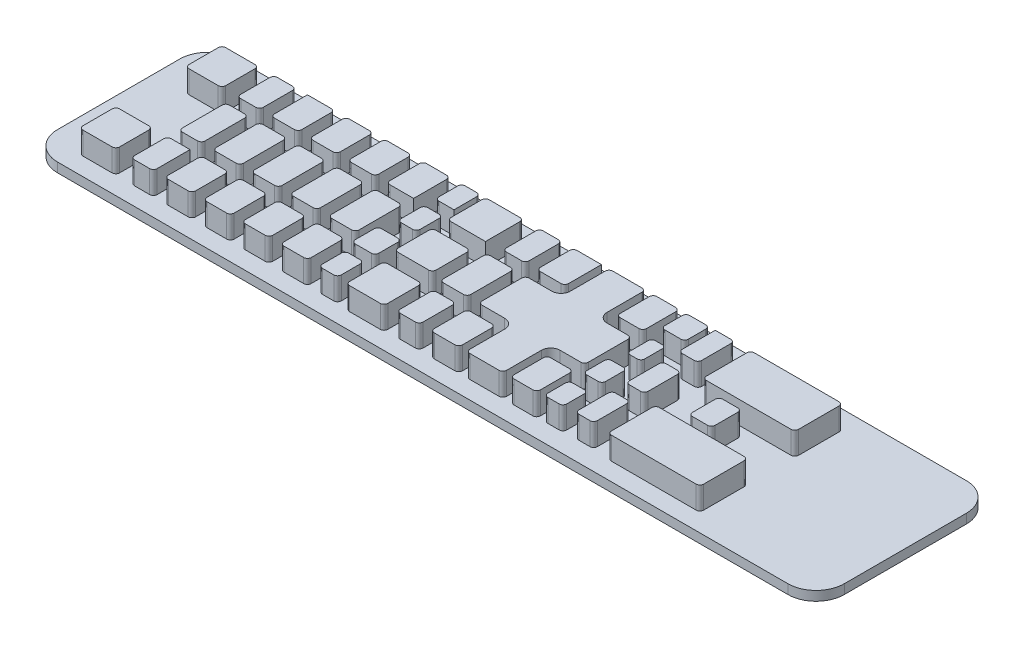
SolidWorks part; units mm, degrees
material "PVB"
ref_plane "Front Plane" through (0, 0, 0) normal (0, 0, 1) x (1, 0, 0)
ref_plane "Top Plane" through (0, 0, 0) normal (0, 1, 0) x (1, 0, 0)
ref_plane "Right Plane" through (0, 0, 0) normal (1, 0, 0) x (0, 0, -1)
ref_axis "X-axis" through (-88.99, 0, 0) along (1, 0, 0)
ref_axis "Y-axis" through (0, 55, 0) along (0, -1, 0)
ref_axis "Z-axis" through (0, 0, -88.99) along (0, 0, 1)
sketch "Sketch1" plane through (0, 0, 0) normal (0, 1, 0) x (1, 0, 0)
  line L1 (107.95, 25.4) -> (-107.95, 25.4)
  line L2 (107.95, 25.4) -> (107.95, -25.4)
  line L3 (107.95, -25.4) -> (-107.95, -25.4)
  line L4 (-107.95, 25.4) -> (-107.95, -25.4)
  line L5 (107.95, 25.4) -> (-107.95, -25.4) construction
  line L6 (107.95, -25.4) -> (-107.95, 25.4) construction
  point P0 (0, 0)
  dimension "D1" = 215.9
  dimension "D2" = 50.8
extrude "Boss-Extrude1" add sketch "Sketch1" along normal blind 2.54
sketch "Sketch4" plane through (0, 2.54, 0) normal (0, 1, 0) x (1, 0, 0)
  line L0 (-98.044, 19.304) -> (-98.044, 9.398)
  line L1 (107.95, 25.4) -> (-107.95, 25.4) construction
  line L2 (-107.95, -25.4) -> (107.95, -25.4) construction
  line L3 (-107.95, 25.4) -> (-107.95, -25.4) construction
  line L4 (-88.138, 19.304) -> (-88.138, 9.398)
  line L5 (-84.074, 19.304) -> (-84.074, 9.398)
  line L6 (-77.978, 19.304) -> (-77.978, 9.398)
  line L7 (-74.93, 19.304) -> (-74.93, 9.398)
  line L8 (-67.564, 19.304) -> (-67.564, 9.398)
  line L9 (-64.516, 19.304) -> (-64.516, 9.398)
  line L10 (-57.15, 19.304) -> (-57.15, 9.398)
  line L11 (-54.102, 19.304) -> (-54.102, 9.398)
  line L12 (-46.736, 19.304) -> (-46.736, 9.398)
  line L13 (-43.688, 19.304) -> (-43.688, 9.398)
  line L14 (-36.322, 19.304) -> (-36.322, 9.398)
  line L15 (-33.274, 19.304) -> (-33.274, 12.192)
  line L16 (36.83, 19.304) -> (36.83, 9.398)
  line L17 (33.782, 19.304) -> (33.782, 12.192)
  line L18 (28.702, 19.304) -> (28.702, 12.192)
  line L19 (25.654, 19.304) -> (25.654, 9.398)
  line L20 (18.542, 19.304) -> (18.542, 9.398)
  line L21 (16.51, 19.304) -> (16.51, 6.35)
  line L22 (6.604, 19.304) -> (6.604, 6.35)
  line L23 (-28.194, 19.304) -> (-28.194, 12.192)
  line L24 (-25.146, 19.304) -> (-25.146, 9.398)
  line L25 (-15.24, 19.304) -> (-15.24, 8.8607)
  line L26 (-12.192, 19.304) -> (-12.192, -6.35)
  line L27 (-6.096, 19.304) -> (-6.096, -6.35)
  line L28 (-3.048, 19.304) -> (-3.048, 9.398)
  line L29 (4.572, 19.304) -> (4.572, 9.398)
  line L30 (-98.044, 19.304) -> (-88.138, 19.304)
  line L31 (-98.044, -19.304) -> (-88.138, -19.304)
  line L32 (-98.044, -9.398) -> (-88.138, -9.398)
  line L33 (-98.044, 9.398) -> (-88.138, 9.398)
  line L34 (-33.274, 9.144) -> (-28.194, 9.144)
  line L35 (-33.274, -9.144) -> (-28.194, -9.144)
  line L36 (-84.074, -19.304) -> (-77.978, -19.304)
  line L37 (-84.074, -9.398) -> (-77.978, -9.398)
  line L38 (-84.074, -6.35) -> (-77.978, -6.35)
  line L39 (-84.074, 9.398) -> (-77.978, 9.398)
  line L40 (-84.074, 6.35) -> (-77.978, 6.35)
  line L41 (-84.074, 19.304) -> (-77.978, 19.304)
  line L42 (-43.688, -19.304) -> (-36.322, -19.304)
  line L43 (-43.688, -9.398) -> (-36.322, -9.398)
  line L44 (-43.688, -6.35) -> (-36.322, -6.35)
  line L45 (-43.688, 6.35) -> (-36.322, 6.35)
  line L46 (-43.688, 9.398) -> (-36.322, 9.398)
  line L47 (-54.102, -19.304) -> (-46.736, -19.304)
  line L48 (-54.102, -9.398) -> (-46.736, -9.398)
  line L49 (-54.102, -6.35) -> (-46.736, -6.35)
  line L50 (-54.102, 6.35) -> (-46.736, 6.35)
  line L51 (-54.102, 9.398) -> (-46.736, 9.398)
  line L52 (-64.516, -19.304) -> (-57.15, -19.304)
  line L53 (-64.516, -9.398) -> (-57.15, -9.398)
  line L54 (-64.516, -6.35) -> (-57.15, -6.35)
  line L55 (-64.516, 6.35) -> (-57.15, 6.35)
  line L56 (-64.516, 9.398) -> (-57.15, 9.398)
  line L57 (-74.93, -19.304) -> (-67.564, -19.304)
  line L58 (-74.93, -9.398) -> (-67.564, -9.398)
  line L59 (-74.93, -6.35) -> (-67.564, -6.35)
  line L60 (-74.93, 6.35) -> (-67.564, 6.35)
  line L61 (-74.93, 9.398) -> (-67.564, 9.398)
  line L62 (-74.93, 19.304) -> (-67.564, 19.304)
  line L63 (-64.516, 19.304) -> (-57.15, 19.304)
  line L64 (-54.102, 19.304) -> (-46.736, 19.304)
  line L65 (-43.688, 19.304) -> (-36.322, 19.304)
  line L66 (-98.044, -9.398) -> (-98.044, -19.304)
  line L67 (-88.138, -9.398) -> (-88.138, -19.304)
  line L68 (-33.274, 12.192) -> (-28.194, 12.192)
  line L69 (-33.274, -2.032) -> (-28.194, -2.032)
  line L70 (-33.274, 2.032) -> (-28.194, 2.032)
  line L71 (-33.274, -12.192) -> (-28.194, -12.192)
  line L72 (-33.274, 19.304) -> (-28.194, 19.304)
  line L73 (-33.274, -19.304) -> (-28.194, -19.304)
  line L74 (-84.074, -9.398) -> (-84.074, -19.304)
  line L75 (-77.978, -9.398) -> (-77.978, -19.304)
  line L76 (-74.93, -9.398) -> (-74.93, -19.304)
  line L77 (-67.564, -9.398) -> (-67.564, -19.304)
  line L78 (-64.516, -9.398) -> (-64.516, -19.304)
  line L79 (-57.15, -9.398) -> (-57.15, -19.304)
  line L80 (-54.102, -9.398) -> (-54.102, -19.304)
  line L81 (-46.736, -9.398) -> (-46.736, -19.304)
  line L82 (-43.688, -9.398) -> (-43.688, -19.304)
  line L83 (-36.322, -9.398) -> (-36.322, -19.304)
  line L84 (-36.322, 6.35) -> (-36.322, -6.35)
  line L85 (-43.688, 6.35) -> (-43.688, -6.35)
  line L86 (-46.736, 6.35) -> (-46.736, -6.35)
  line L87 (-54.102, 6.35) -> (-54.102, -6.35)
  line L88 (-57.15, 6.35) -> (-57.15, -6.35)
  line L89 (-64.516, 6.35) -> (-64.516, -6.35)
  line L90 (-67.564, 6.35) -> (-67.564, -6.35)
  line L91 (-74.93, 6.35) -> (-74.93, -6.35)
  line L92 (-77.978, 6.35) -> (-77.978, -6.35)
  line L93 (-84.074, 6.35) -> (-84.074, -6.35)
  line L94 (-33.274, -12.192) -> (-33.274, -19.304)
  line L95 (-28.194, -12.192) -> (-28.194, -19.304)
  line L96 (-28.194, -2.032) -> (-28.194, -9.144)
  line L97 (-33.274, -2.032) -> (-33.274, -9.144)
  line L98 (-33.274, 9.144) -> (-33.274, 2.032)
  line L99 (-28.194, 9.144) -> (-28.194, 2.032)
  line L100 (-25.146, -19.304) -> (-15.24, -19.304)
  line L101 (-25.146, -9.398) -> (-15.24, -9.398)
  line L102 (-25.146, -6.35) -> (-15.24, -6.35)
  line L103 (-25.146, 6.35) -> (-15.24, 6.35)
  line L104 (-25.146, 9.398) -> (-15.24, 9.398)
  line L105 (-25.146, 19.304) -> (-15.24, 19.304)
  line L106 (-25.146, -9.398) -> (-25.146, -19.304)
  line L107 (-15.24, -9.398) -> (-15.24, -19.304)
  line L108 (-25.146, 6.35) -> (-25.146, -6.35)
  line L109 (-12.192, 19.304) -> (-6.096, 19.304)
  line L110 (-6.096, 19.304) -> (-6.096, 9.398)
  line L111 (-6.096, 9.398) -> (-12.192, 9.398)
  line L112 (-12.192, 9.398) -> (-12.192, 19.304)
  line L113 (-12.192, 6.35) -> (-6.096, 6.35)
  line L114 (-6.096, 6.35) -> (-6.096, -6.35)
  line L115 (-6.096, -6.35) -> (-12.192, -6.35)
  line L116 (-12.192, -6.35) -> (-12.192, 6.35)
  line L117 (-15.24, 6.35) -> (-15.24, -6.35)
  line L118 (-15.24, 9.398) -> (-15.24, 19.304)
  line L119 (-12.192, -9.398) -> (-6.096, -9.398)
  line L120 (-6.096, -9.398) -> (-6.096, -19.304)
  line L121 (-6.096, -19.304) -> (-12.192, -19.304)
  line L122 (-12.192, -19.304) -> (-12.192, -9.398)
  line L123 (-3.048, -19.304) -> (4.572, -19.304)
  line L124 (4.572, -19.304) -> (4.572, -9.398)
  line L125 (4.572, -9.398) -> (-3.048, -9.398)
  line L126 (-3.048, -9.398) -> (-3.048, -19.304)
  line L127 (-3.048, 9.398) -> (4.572, 9.398)
  line L128 (4.572, 9.398) -> (4.572, 19.304)
  line L129 (4.572, 19.304) -> (-3.048, 19.304)
  line L130 (-3.048, 19.304) -> (-3.048, 9.398)
  line L131 (-3.048, 6.35) -> (3.302, 6.35)
  line L132 (-3.048, 6.35) -> (-3.048, -6.35)
  line L134 (6.604, -19.304) -> (16.51, -19.304)
  line L135 (16.51, -19.304) -> (16.51, -8.89)
  line L136 (19.05, -6.35) -> (25.654, -6.35)
  line L137 (25.654, -6.35) -> (25.654, 6.35)
  line L138 (25.654, 6.35) -> (19.05, 6.35)
  line L139 (16.51, 8.89) -> (16.51, 19.304)
  line L140 (16.51, 19.304) -> (6.604, 19.304)
  line L141 (6.604, 19.304) -> (6.604, 8.89)
  line L142 (4.064, 6.35) -> (3.302, 6.35)
  line L143 (6.604, -19.304) -> (6.604, -8.89)
  line L145 (18.542, -19.304) -> (25.654, -19.304)
  line L146 (25.654, -19.304) -> (25.654, -9.398)
  line L147 (25.654, -9.398) -> (18.542, -9.398)
  line L148 (18.542, -9.398) -> (18.542, -19.304)
  line L149 (18.542, 9.398) -> (25.654, 9.398)
  line L150 (25.654, 9.398) -> (25.654, 19.304)
  line L151 (25.654, 19.304) -> (18.542, 19.304)
  line L152 (18.542, 19.304) -> (18.542, 9.398)
  line L153 (41.8338, 19.304) -> (41.8338, 9.398)
  line L154 (44.8818, 19.304) -> (44.8818, 6.35)
  line L155 (36.83, -19.304) -> (41.8338, -19.304)
  line L156 (41.8338, -19.304) -> (41.8338, -9.398)
  line L157 (41.8338, -9.398) -> (36.83, -9.398)
  line L158 (36.83, -9.398) -> (36.83, -19.304)
  line L159 (36.83, -6.35) -> (41.8338, -6.35)
  line L160 (41.8338, -6.35) -> (41.8338, 6.35)
  line L161 (41.8338, 6.35) -> (36.83, 6.35)
  line L162 (36.83, 6.35) -> (36.83, -6.35)
  line L163 (36.83, 19.304) -> (41.8338, 19.304)
  line L164 (41.8338, 19.304) -> (41.8338, 9.398)
  line L165 (41.8338, 9.398) -> (36.83, 9.398)
  line L166 (36.83, 9.398) -> (36.83, 19.304)
  line L167 (28.702, -12.192) -> (33.782, -12.192)
  line L168 (33.782, -12.192) -> (33.782, -19.304)
  line L169 (33.782, -19.304) -> (28.702, -19.304)
  line L170 (28.702, -19.304) -> (28.702, -12.192)
  line L171 (28.702, -9.144) -> (33.782, -9.144)
  line L172 (33.782, -9.144) -> (33.782, -2.032)
  line L173 (33.782, -2.032) -> (28.702, -2.032)
  line L174 (28.702, -2.032) -> (28.702, -9.144)
  line L175 (28.702, 2.032) -> (33.782, 2.032)
  line L176 (33.782, 2.032) -> (33.782, 9.144)
  line L177 (33.782, 9.144) -> (28.702, 9.144)
  line L178 (28.702, 9.144) -> (28.702, 2.032)
  line L179 (28.702, 12.192) -> (33.782, 12.192)
  line L180 (33.782, 12.192) -> (33.782, 19.304)
  line L181 (33.782, 19.304) -> (28.702, 19.304)
  line L182 (28.702, 19.304) -> (28.702, 12.192)
  line L183 (6.604, -6.35) -> (6.604, -19.304)
  line L184 (4.572, -9.398) -> (4.572, -19.304)
  line L185 (16.51, -6.35) -> (16.51, -19.304)
  line L186 (18.542, -9.398) -> (18.542, -19.304)
  line L187 (-3.048, -9.398) -> (-3.048, -19.304)
  line L188 (-6.096, -9.398) -> (-6.096, -19.304)
  line L189 (-12.192, -9.398) -> (-12.192, -19.304)
  line L190 (-3.048, 6.35) -> (-3.048, -6.35)
  line L191 (25.654, 6.35) -> (25.654, -6.35)
  line L192 (25.654, -9.398) -> (25.654, -19.304)
  line L193 (28.702, 9.144) -> (28.702, 2.032)
  line L194 (33.782, 9.144) -> (33.782, 2.032)
  line L195 (28.702, -2.032) -> (28.702, -9.144)
  line L196 (33.782, -2.032) -> (33.782, -9.144)
  line L197 (28.702, -12.192) -> (28.702, -19.304)
  line L198 (33.782, -12.192) -> (33.782, -19.304)
  line L199 (36.83, -9.398) -> (36.83, -19.304)
  line L200 (41.8338, -9.398) -> (41.8338, -19.304)
  line L201 (36.83, 6.35) -> (36.83, -6.35)
  line L202 (41.8338, 6.35) -> (41.8338, -6.35)
  line L203 (44.8818, -19.304) -> (69.7992, -19.304)
  line L204 (-3.048, -6.35) -> (4.064, -6.35)
  line L205 (44.8818, 19.304) -> (69.7992, 19.304)
  line L206 (69.7992, 6.35) -> (44.8818, 6.35)
  line L207 (44.8818, -6.35) -> (69.7992, -6.35)
  line L208 (51.4858, -3.9841) -> (57.5818, -3.9841)
  line L209 (51.4858, 4.1693) -> (57.5818, 4.1693)
  line L212 (69.7992, 19.304) -> (69.7992, 6.35)
  line L215 (57.5818, 4.1693) -> (57.5818, -3.9841)
  line L216 (51.4858, 4.1693) -> (51.4858, -3.9841)
  line L217 (44.8818, -6.35) -> (44.8818, -19.304)
  line L220 (69.7992, -6.35) -> (69.7992, -19.304)
  arc A0 (19.05, 6.35) -> (16.51, 8.89) centre (19.05, 8.89) cw
  arc A1 (16.51, -8.89) -> (19.05, -6.35) centre (19.05, -8.89) cw
  arc A2 (6.604, 8.89) -> (4.064, 6.35) centre (4.064, 8.89) cw
  arc A3 (6.604, -8.89) -> (4.064, -6.35) centre (4.064, -8.89) ccw
  dimension "D40" = 2.54
  dimension "D41" = 2.54
  dimension "D44" = 2.54
  dimension "D45" = 2.54
  dimension "D1" = 9.906
  dimension "D2" = 9.906
  dimension "D3" = 4.064
  dimension "D4" = 6.096
  dimension "D5" = 3.048
  dimension "D6" = 7.366
  dimension "D7" = 3.048
  dimension "D8" = 7.366
  dimension "D9" = 3.048
  dimension "D10" = 7.366
  dimension "D11" = 3.048
  dimension "D12" = 7.366
  dimension "D13" = 8.1534
  dimension "D14" = 5.08
  dimension "D15" = 3.048
  dimension "D16" = 9.906
  dimension "D17" = 3.048
  dimension "D18" = 6.096
  dimension "D19" = 3.048
  dimension "D20" = 7.62
  dimension "D21" = 6.096
  dimension "D22" = 6.096
  dimension "D23" = 9.906
  dimension "D24" = 9.906
  dimension "D25" = 7.112
  dimension "D26" = 3.048
  dimension "D27" = 7.112
  dimension "D28" = 3.048
  dimension "D29" = 7.112
  dimension "D30" = 7.112
  dimension "D31" = 2.032
  dimension "D32" = 9.906
  dimension "D33" = 2.032
  dimension "D34" = 7.112
  dimension "D35" = 3.048
  dimension "D36" = 5.08
  dimension "D37" = 3.048
  dimension "D38" = 3.048
  dimension "D39" = 5.0038
  dimension "D42" = 12.954
  dimension "D43" = 12.954
  dimension "D46" = 24.9174
  dimension "D47" = 7.112
  dimension "D48" = 7.112
sketch "Sketch5" plane through (0, 2.54, 0) normal (0, 1, 0) x (1, 0, 0)
  line L0 (6.604, 19.304) -> (6.604, 8.89)
  line L1 (-98.044, 9.398) -> (-88.138, 9.398)
  line L2 (-98.044, 9.398) -> (-98.044, 19.304)
  line L3 (-98.044, 19.304) -> (-88.138, 19.304)
  line L4 (-88.138, 9.398) -> (-88.138, 19.304)
  line L5 (-98.044, -19.304) -> (-88.138, -19.304)
  line L6 (-98.044, -19.304) -> (-98.044, -9.398)
  line L7 (-98.044, -9.398) -> (-88.138, -9.398)
  line L8 (-88.138, -19.304) -> (-88.138, -9.398)
  line L9 (-84.074, -19.304) -> (-77.978, -19.304)
  line L10 (-84.074, -19.304) -> (-84.074, -9.398)
  line L11 (-84.074, -9.398) -> (-77.978, -9.398)
  line L12 (-77.978, -19.304) -> (-77.978, -9.398)
  line L13 (-84.074, -6.35) -> (-77.978, -6.35)
  line L14 (-84.074, -6.35) -> (-84.074, 6.35)
  line L15 (-84.074, 6.35) -> (-77.978, 6.35)
  line L16 (-77.978, -6.35) -> (-77.978, 6.35)
  line L17 (-84.074, 9.398) -> (-77.978, 9.398)
  line L18 (-84.074, 9.398) -> (-84.074, 19.304)
  line L19 (-84.074, 19.304) -> (-77.978, 19.304)
  line L20 (-77.978, 9.398) -> (-77.978, 19.304)
  line L21 (-74.93, 9.398) -> (-67.564, 9.398)
  line L22 (-74.93, 9.398) -> (-74.93, 19.304)
  line L23 (-74.93, 19.304) -> (-67.564, 19.304)
  line L24 (-67.564, 9.398) -> (-67.564, 19.304)
  line L25 (-74.93, -6.35) -> (-67.564, -6.35)
  line L26 (-74.93, -6.35) -> (-74.93, 6.35)
  line L27 (-74.93, 6.35) -> (-67.564, 6.35)
  line L28 (-67.564, -6.35) -> (-67.564, 6.35)
  line L29 (-74.93, -19.304) -> (-67.564, -19.304)
  line L30 (-74.93, -19.304) -> (-74.93, -9.398)
  line L31 (-74.93, -9.398) -> (-67.564, -9.398)
  line L32 (-67.564, -19.304) -> (-67.564, -9.398)
  line L33 (-64.516, -19.304) -> (-57.15, -19.304)
  line L34 (-64.516, -19.304) -> (-64.516, -9.398)
  line L35 (-64.516, -9.398) -> (-57.15, -9.398)
  line L36 (-57.15, -19.304) -> (-57.15, -9.398)
  line L37 (-64.516, -6.35) -> (-57.15, -6.35)
  line L38 (-64.516, -6.35) -> (-64.516, 6.35)
  line L39 (-64.516, 6.35) -> (-57.15, 6.35)
  line L40 (-57.15, -6.35) -> (-57.15, 6.35)
  line L41 (-64.516, 9.398) -> (-57.15, 9.398)
  line L42 (-64.516, 9.398) -> (-64.516, 19.304)
  line L43 (-64.516, 19.304) -> (-57.15, 19.304)
  line L44 (-57.15, 9.398) -> (-57.15, 19.304)
  line L45 (-54.102, 9.398) -> (-46.736, 9.398)
  line L46 (-54.102, 9.398) -> (-54.102, 19.304)
  line L47 (-54.102, 19.304) -> (-46.736, 19.304)
  line L48 (-46.736, 9.398) -> (-46.736, 19.304)
  line L49 (-54.102, -6.35) -> (-46.736, -6.35)
  line L50 (-54.102, -6.35) -> (-54.102, 6.35)
  line L51 (-54.102, 6.35) -> (-46.736, 6.35)
  line L52 (-46.736, -6.35) -> (-46.736, 6.35)
  line L53 (-54.102, -19.304) -> (-46.736, -19.304)
  line L54 (-54.102, -19.304) -> (-54.102, -9.398)
  line L55 (-54.102, -9.398) -> (-46.736, -9.398)
  line L56 (-46.736, -19.304) -> (-46.736, -9.398)
  line L57 (-43.688, -19.304) -> (-36.322, -19.304)
  line L58 (-43.688, -19.304) -> (-43.688, -9.398)
  line L59 (-43.688, -9.398) -> (-36.322, -9.398)
  line L60 (-36.322, -19.304) -> (-36.322, -9.398)
  line L61 (-43.688, -6.35) -> (-36.322, -6.35)
  line L62 (-43.688, -6.35) -> (-43.688, 6.35)
  line L63 (-43.688, 6.35) -> (-36.322, 6.35)
  line L64 (-36.322, -6.35) -> (-36.322, 6.35)
  line L65 (-43.688, 9.398) -> (-36.322, 9.398)
  line L66 (-43.688, 9.398) -> (-43.688, 19.304)
  line L67 (-43.688, 19.304) -> (-36.322, 19.304)
  line L68 (-36.322, 9.398) -> (-36.322, 19.304)
  line L69 (-33.274, 12.192) -> (-28.194, 12.192)
  line L70 (-33.274, 12.192) -> (-33.274, 19.304)
  line L71 (-33.274, 19.304) -> (-28.194, 19.304)
  line L72 (-28.194, 12.192) -> (-28.194, 19.304)
  line L73 (-33.274, 2.032) -> (-28.194, 2.032)
  line L74 (-33.274, 2.032) -> (-33.274, 9.144)
  line L75 (-33.274, 9.144) -> (-28.194, 9.144)
  line L76 (-28.194, 2.032) -> (-28.194, 9.144)
  line L77 (-34.544, -9.144) -> (-28.194, -9.144)
  line L78 (-34.544, -9.144) -> (-34.544, -2.032)
  line L79 (-34.544, -2.032) -> (-28.194, -2.032)
  line L80 (-28.194, -9.144) -> (-28.194, -2.032)
  line L81 (-26.797, -5.334) -> (-16.51, -5.334)
  line L82 (-26.797, -5.334) -> (-26.797, 4.953)
  line L83 (-26.797, 4.953) -> (-16.51, 4.953)
  line L84 (-16.51, -5.334) -> (-16.51, 4.953)
  line L85 (-26.797, 9.017) -> (-16.51, 9.017)
  line L86 (-26.797, 9.017) -> (-26.797, 19.304)
  line L87 (-26.797, 19.304) -> (-16.51, 19.304)
  line L88 (-16.51, 9.017) -> (-16.51, 19.304)
  line L89 (-12.192, 9.398) -> (-6.096, 9.398)
  line L90 (-12.192, 9.398) -> (-12.192, 19.304)
  line L91 (-12.192, 19.304) -> (-6.096, 19.304)
  line L92 (-6.096, 9.398) -> (-6.096, 19.304)
  line L93 (-3.048, 9.398) -> (4.572, 9.398)
  line L94 (-3.048, 9.398) -> (-3.048, 19.304)
  line L95 (-3.048, 19.304) -> (4.572, 19.304)
  line L96 (4.572, 9.398) -> (4.572, 19.304)
  line L97 (-13.462, -6.35) -> (-6.096, -6.35)
  line L98 (-13.462, -6.35) -> (-13.462, 6.35)
  line L99 (-13.462, 6.35) -> (-6.096, 6.35)
  line L100 (-6.096, -6.35) -> (-6.096, 6.35)
  line L101 (-33.274, -19.304) -> (-28.194, -19.304)
  line L102 (-33.274, -19.304) -> (-33.274, -12.192)
  line L103 (-33.274, -12.192) -> (-28.194, -12.192)
  line L104 (-28.194, -19.304) -> (-28.194, -12.192)
  line L105 (-25.527, -19.685) -> (-15.24, -19.685)
  line L106 (-25.527, -19.685) -> (-25.527, -9.398)
  line L107 (-25.527, -9.398) -> (-15.24, -9.398)
  line L108 (-15.24, -19.685) -> (-15.24, -9.398)
  line L109 (-12.192, -19.304) -> (-6.096, -19.304)
  line L110 (-12.192, -19.304) -> (-12.192, -9.398)
  line L111 (-12.192, -9.398) -> (-6.096, -9.398)
  line L112 (-6.096, -19.304) -> (-6.096, -9.398)
  line L113 (-3.048, -19.304) -> (4.572, -19.304)
  line L114 (-3.048, -19.304) -> (-3.048, -9.398)
  line L115 (-3.048, -9.398) -> (4.572, -9.398)
  line L116 (4.572, -19.304) -> (4.572, -9.398)
  line L117 (18.542, -19.304) -> (25.654, -19.304)
  line L118 (18.542, -19.304) -> (18.542, -9.398)
  line L119 (18.542, -9.398) -> (25.654, -9.398)
  line L120 (25.654, -19.304) -> (25.654, -9.398)
  line L121 (27.432, -19.05) -> (32.512, -19.05)
  line L122 (27.432, -19.05) -> (27.432, -12.319)
  line L123 (27.432, -12.319) -> (32.512, -12.319)
  line L124 (32.512, -19.05) -> (32.512, -12.319)
  line L125 (35.56, -18.796) -> (40.5638, -18.796)
  line L126 (35.56, -18.796) -> (35.56, -8.89)
  line L127 (35.56, -8.89) -> (40.5638, -8.89)
  line L128 (40.5638, -18.796) -> (40.5638, -8.89)
  line L129 (27.432, -8.509) -> (32.512, -8.509)
  line L130 (27.432, -8.509) -> (27.432, -1.778)
  line L131 (27.432, -1.778) -> (32.512, -1.778)
  line L132 (32.512, -8.509) -> (32.512, -1.778)
  line L133 (28.702, 2.032) -> (32.512, 2.032)
  line L134 (28.702, 2.032) -> (28.702, 8.763)
  line L135 (28.702, 8.763) -> (32.512, 8.763)
  line L136 (32.512, 2.032) -> (32.512, 8.763)
  line L137 (27.432, 12.573) -> (33.782, 12.573)
  line L138 (27.432, 12.573) -> (27.432, 19.304)
  line L139 (27.432, 19.304) -> (33.782, 19.304)
  line L140 (33.782, 12.573) -> (33.782, 19.304)
  line L141 (18.542, 9.398) -> (25.654, 9.398)
  line L142 (18.542, 9.398) -> (18.542, 19.304)
  line L143 (18.542, 19.304) -> (25.654, 19.304)
  line L144 (25.654, 9.398) -> (25.654, 19.304)
  line L145 (35.3337, 9.398) -> (40.5638, 9.398)
  line L146 (35.3337, 9.398) -> (35.3337, 19.304)
  line L147 (35.3337, 19.304) -> (40.5638, 19.304)
  line L148 (40.5638, 9.398) -> (40.5638, 19.304)
  line L149 (35.56, -5.08) -> (40.5638, -5.08)
  line L150 (35.56, -5.08) -> (35.56, 4.826)
  line L151 (35.56, 4.826) -> (40.5638, 4.826)
  line L152 (40.5638, -5.08) -> (40.5638, 4.826)
  line L153 (51.4858, -3.9841) -> (57.5818, -3.9841)
  line L154 (51.4858, -3.9841) -> (51.4858, 4.1693)
  line L155 (51.4858, 4.1693) -> (57.5818, 4.1693)
  line L156 (57.5818, -3.9841) -> (57.5818, 4.1693)
  line L157 (44.8818, -19.304) -> (69.7992, -19.304)
  line L158 (44.8818, -19.304) -> (44.8818, -6.35)
  line L159 (44.8818, -6.35) -> (69.7992, -6.35)
  line L160 (69.7992, -19.304) -> (69.7992, -6.35)
  line L161 (44.8818, 6.35) -> (69.7992, 6.35)
  line L162 (44.8818, 6.35) -> (44.8818, 19.304)
  line L163 (44.8818, 19.304) -> (69.7992, 19.304)
  line L164 (69.7992, 6.35) -> (69.7992, 19.304)
  line L165 (4.064, 6.35) -> (-3.048, 6.35)
  line L166 (-3.048, 6.35) -> (-3.048, -6.35)
  line L167 (-3.048, -6.35) -> (4.064, -6.35)
  line L168 (6.604, -8.89) -> (6.604, -19.304)
  line L169 (6.604, -19.304) -> (16.51, -19.304)
  line L170 (16.51, -19.304) -> (16.51, -8.89)
  line L171 (19.05, -6.35) -> (25.654, -6.35)
  line L172 (25.654, -6.35) -> (25.654, 6.35)
  line L173 (25.654, 6.35) -> (19.05, 6.35)
  line L174 (16.51, 8.89) -> (16.51, 19.304)
  line L175 (16.51, 19.304) -> (6.604, 19.304)
  arc A0 (16.51, -8.89) -> (19.05, -6.35) centre (19.05, -8.89) cw
  arc A1 (19.05, 6.35) -> (16.51, 8.89) centre (19.05, 8.89) cw
  arc A2 (6.604, 8.89) -> (4.064, 6.35) centre (4.064, 8.89) cw
  arc A3 (4.064, -6.35) -> (6.604, -8.89) centre (4.064, -8.89) cw
  point P190 (6.604, 6.35)
  point P203 (6.604, -6.35)
  dimension "D11" = 2.54
  dimension "D1" = 5.08
  dimension "D2" = 6.731
  dimension "D3" = 6.731
  dimension "D4" = 6.731
  dimension "D5" = 3.81
  dimension "D6" = 3.81
  dimension "D7" = 9.906
  dimension "D8" = 4.572
  dimension "D9" = 3.81
  dimension "D10" = 9.906
  dimension "D12" = 10.287
  dimension "D13" = 7.112
  dimension "D14" = 10.287
  dimension "D15" = 4.064
  dimension "D16" = 4.064
extrude "Boss-Extrude4" add sketch "Sketch5" along normal blind 6.096
fillet "Fillet10" radius 1.016 47 edges at (40.5638, 5.588, -4.826) (32.512, 5.588, -8.763) (33.782, 5.588, -19.304) (40.5638, 5.588, -19.304) (18.542, 5.588, -19.304) (25.654, 5.588, -19.304) (27.432, 5.588, -19.304) (28.702, 5.588, -8.763) (27.432, 5.588, 1.778) (27.432, 5.588, 12.319) (25.654, 5.588, 9.398) (33.782, 5.588, -12.573) (32.512, 5.588, -2.032) (32.512, 5.588, 1.778) (32.512, 5.588, 12.319) (32.512, 5.588, 8.509) (25.654, 5.588, 19.304) (18.542, 5.588, 19.304) (18.542, 5.588, 9.398) (18.542, 5.588, -9.398) (25.654, 5.588, -9.398) (27.432, 5.588, -12.573) (28.702, 5.588, -2.032) (27.432, 5.588, 8.509) (27.432, 5.588, 19.05) (32.512, 5.588, 19.05) (35.56, 5.588, -4.826) (40.5638, 5.588, -9.398) (35.3337, 5.588, -9.398) (35.56, 5.588, 5.08) (35.56, 5.588, 8.89) (35.56, 5.588, 18.796) (40.5638, 5.588, 18.796) (40.5638, 5.588, 5.08) (40.5638, 5.588, 8.89) (44.8818, 5.588, -6.35) (44.8818, 5.588, -19.304) (69.7992, 5.588, -19.304) (69.7992, 5.588, -6.35) (57.5818, 5.588, -4.1693) (51.4858, 5.588, -4.1693) (57.5818, 5.588, 3.9841) (51.4858, 5.588, 3.9841) (44.8818, 5.588, 6.35) (44.8818, 5.588, 19.304) (69.7992, 5.588, 6.35) (69.7992, 5.588, 19.304)
fillet "Fillet11" radius 1.016 118 edges at (-88.138, 5.588, -9.398) (-88.138, 5.588, 9.398) (-98.044, 5.588, -9.398) (-98.044, 5.588, -19.304) (-88.138, 5.588, -19.304) (-84.074, 5.588, -19.304) (-77.978, 5.588, -6.35) (-67.564, 5.588, -6.35) (-64.516, 5.588, -19.304) (-77.978, 5.588, -19.304) (-67.564, 5.588, -19.304) (-57.15, 5.588, -9.398) (-57.15, 5.588, -6.35) (-34.544, 5.588, 9.144) (-57.15, 5.588, 6.35) (-46.736, 5.588, 6.35) (-67.564, 5.588, 9.398) (-67.564, 5.588, 6.35) (-64.516, 5.588, 6.35) (-67.564, 5.588, -9.398) (-64.516, 5.588, -9.398) (-64.516, 5.588, -6.35) (-74.93, 5.588, -6.35) (-74.93, 5.588, -9.398) (-77.978, 5.588, -9.398) (-84.074, 5.588, -9.398) (-84.074, 5.588, -6.35) (-84.074, 5.588, 6.35) (-77.978, 5.588, 6.35) (-74.93, 5.588, 6.35) (-74.93, 5.588, 9.398) (-67.564, 5.588, 19.304) (-74.93, 5.588, 19.304) (-77.978, 5.588, 19.304) (-88.138, 5.588, 19.304) (-84.074, 5.588, 19.304) (-84.074, 5.588, 9.398) (-98.044, 5.588, 9.398) (-98.044, 5.588, 19.304) (-54.102, 5.588, 6.35) (-54.102, 5.588, -6.35) (-54.102, 5.588, -9.398) (-33.274, 5.588, -12.192) (-43.688, 5.588, -9.398) (-43.688, 5.588, 6.35) (4.572, 5.588, -9.398) (-28.194, 5.588, -2.032) (4.572, 5.588, 9.398) (-6.096, 5.588, -9.398) (-6.096, 5.588, -6.35) (-46.736, 5.588, -9.398) (-54.102, 5.588, -19.304) (-57.15, 5.588, -19.304) (-46.736, 5.588, -19.304) (-46.736, 5.588, -6.35) (-36.322, 5.588, 9.398) (-33.274, 5.588, 19.304) (-43.688, 5.588, 19.304) (-64.516, 5.588, 19.304) (-64.516, 5.588, 9.398) (-57.15, 5.588, 9.398) (-54.102, 5.588, 9.398) (-46.736, 5.588, 9.398) (-43.688, 5.588, 9.398) (-33.274, 5.588, -2.032) (-28.194, 5.588, 2.032) (-34.544, 5.588, 2.032) (-33.274, 5.588, 12.192) (-25.527, 5.588, 9.398) (-3.048, 5.588, 9.398) (-12.192, 5.588, 9.398) (-26.797, 5.588, -4.953) (-16.51, 5.588, -4.953) (-13.462, 5.588, -6.35) (-12.192, 5.588, -9.398) (-26.797, 5.588, -9.017) (-28.194, 5.588, -9.144) (-33.274, 5.588, -9.144) (-36.322, 5.588, -6.35) (-43.688, 5.588, -6.35) (-43.688, 5.588, -19.304) (-36.322, 5.588, -19.304) (-33.274, 5.588, -19.304) (-28.194, 5.588, -19.304) (-26.797, 5.588, -19.304) (-16.51, 5.588, -19.304) (-12.192, 5.588, -19.304) (-6.096, 5.588, -19.304) (16.51, 5.588, -19.304) (6.604, 5.588, -19.304) (-3.048, 5.588, -19.304) (-3.048, 5.588, -9.398) (-3.048, 5.588, -6.35) (-15.24, 5.588, 9.398) (-6.096, 5.588, 9.398) (-3.048, 5.588, 6.35) (-6.096, 5.588, 6.35) (-13.462, 5.588, 6.35) (-16.51, 5.588, 5.334) (-26.797, 5.588, 5.334) (-28.194, 5.588, 12.192) (-28.194, 5.588, 9.144) (-36.322, 5.588, 6.35) (-57.15, 5.588, 19.304) (-54.102, 5.588, 19.304) (-46.736, 5.588, 19.304) (-36.322, 5.588, 19.304) (-28.194, 5.588, 19.304) (-25.527, 5.588, 19.685) (-15.24, 5.588, 19.685) (-12.192, 5.588, 19.304) (-6.096, 5.588, 19.304) (-3.048, 5.588, 19.304) (4.572, 5.588, 19.304) (6.604, 5.588, 19.304) (16.51, 5.588, 19.304) (25.654, 5.588, -6.35) (25.654, 5.588, 6.35)
sketch "Sketch6" plane through (0, 2.54, 0) normal (0, 1, 0) x (1, 0, 0)
  line L0 (107.95, -25.4) -> (107.95, 25.4) construction
  line L1 (-107.95, -25.4) -> (107.95, -25.4)
  line L2 (-107.95, -25.4) -> (-107.95, -24.13)
  line L3 (-107.95, -24.13) -> (107.95, -24.13)
  line L4 (107.95, -25.4) -> (107.95, -24.13)
  line L6 (-107.95, 25.4) -> (107.95, 25.4)
  line L7 (-107.95, 25.4) -> (-107.95, 24.13)
  line L8 (-107.95, 24.13) -> (107.95, 24.13)
  line L9 (107.95, 25.4) -> (107.95, 24.13)
  dimension "D1" = 1.27
  dimension "D2" = 1.27
extrude "Cut-Extrude1" cut sketch "Sketch6" against normal blind 2.54
sketch "Sketch7" plane through (0, 2.54, 0) normal (0, 1, 0) x (1, 0, 0)
  line L0 (-107.95, 24.13) -> (107.95, 24.13) construction
  line L1 (107.95, -24.13) -> (106.045, -24.13)
  line L2 (107.95, -24.13) -> (107.95, 24.13)
  line L3 (107.95, 24.13) -> (106.045, 24.13)
  line L4 (106.045, -24.13) -> (106.045, 24.13)
  line L5 (107.95, -24.13) -> (-107.95, -24.13) construction
  line L6 (-107.95, 24.13) -> (-106.68, 24.13)
  line L7 (-107.95, 24.13) -> (-107.95, -24.13)
  line L8 (-107.95, -24.13) -> (-106.68, -24.13)
  line L9 (-106.68, 24.13) -> (-106.68, -24.13)
  dimension "D1" = 1.27
  dimension "D2" = 1.905
extrude "Cut-Extrude2" cut sketch "Sketch7" against normal blind 2.54
fillet "Fillet13" radius 7.62 4 edges at (-106.68, 1.27, 24.13) (-106.68, 1.27, -24.13) (106.045, 1.27, -24.13) (106.045, 1.27, 24.13)
